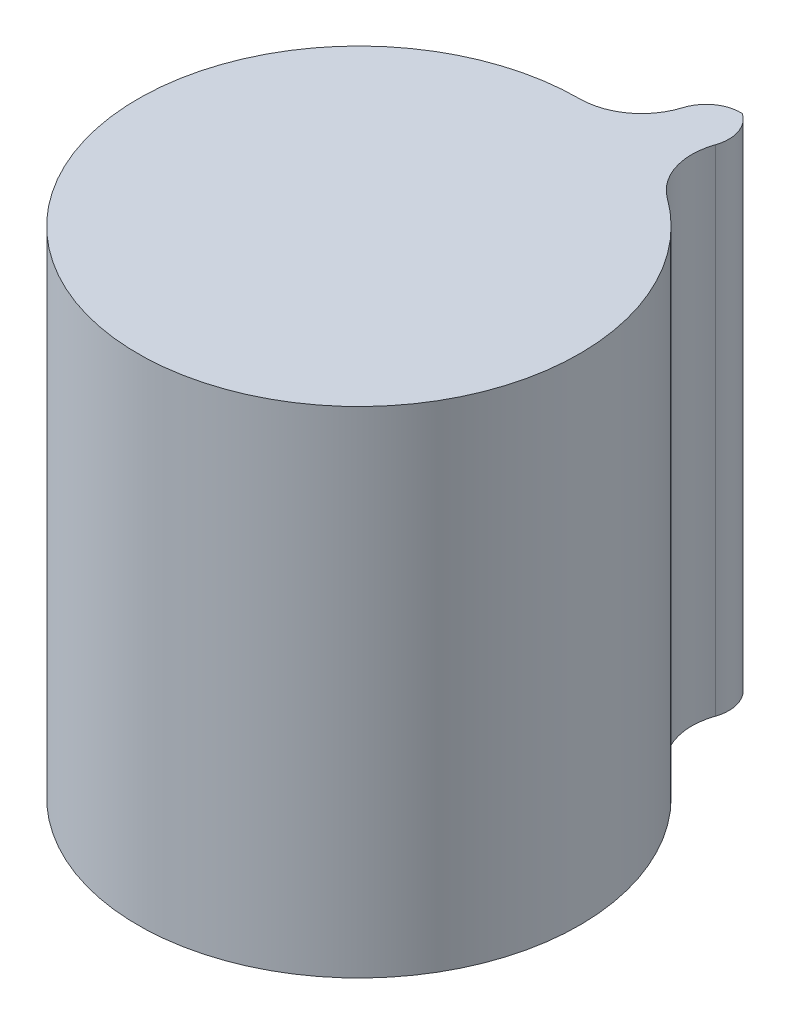
SolidWorks part; units mm, degrees
ref_plane "Front Plane" through (0, 0, 0) normal (0, 0, 1) x (1, 0, 0)
ref_plane "Top Plane" through (0, 0, 0) normal (0, 1, 0) x (1, 0, 0)
ref_plane "Right Plane" through (0, 0, 0) normal (1, 0, 0) x (0, 0, -1)
sketch "Sketch1" plane through (0, 0, 0) normal (0, 1, 0) x (1, 0, 0)
  line L0 (0, 0) -> (0, 4.3928) construction
  line L1 (0, 0) -> (2.388, 3.2869) construction
  circle A0 centre (0, 0) radius 4.3928 construction
  circle A1 centre (0, 0) radius 3.1728 construction
  circle A2 centre (0, 4.0628) radius 0.89 construction
  circle A5 centre (2.388, 3.2869) radius 0.89 construction
  arc A6 (0, 3.1728) -> (0.8515, 3.804) centre (0, 4.0628) ccw
  arc A7 (0.8515, 3.804) -> (1.5007, 4.1285) centre (1.3299, 3.6586) cw
  arc A8 (1.2125, 4.2221) -> (1.547, 3.578) centre (1.0745, 3.7416) cw
  arc A9 (1.8649, 2.5668) -> (1.547, 3.578) centre (2.388, 3.2869) cw
  arc A10 (1.5007, 4.1285) -> (1.2125, 4.2221) centre (0, 0) cw
  arc A11 (0, 3.1728) -> (1.8649, 2.5668) centre (0, 0) ccw
  dimension "D1" = 8.7856
  dimension "D3" = 1.78
  dimension "D4" = 0.5
  dimension "D2" = 1.22
  dimension "D5" = 36
extrude "Boss-Extrude1" add sketch "Sketch1" along normal mid plane 7.112 contours A6 A11 A9 A8 A7 region at (0.0335, 0, -0.1031)
ref_axis "Axis1" through (0, 3.3, 0) along (0, -1, 0)
equation "\"TEETH_NUM\" = 10"
equation "\"TOOTH_PITCH\"= 3mm"
equation "\"PITCH_LINE_OFFSET\"= .015in"
equation "\"DIAMETER_PER_GROOVE\"= \"OUTSIDE_DIAMETER\" / \"TEETH_NUM\" * 1in"
equation "\"PITCH_DIAMETER\"= ( ( \"TEETH_NUM\" * 3 - 1.31 ) / 3.1415 + .415 ) * 1mm"
equation "\"OUTSIDE_DIAMETER\"= \"PITCH_DIAMETER\" - \"PITCH_LINE_OFFSET\" * 2"
equation "\"D1@Sketch1\"=\"OUTSIDE_DIAMETER\""
equation "\"TOOTH_HEIGHT\"= 1.22mm"
equation "\"D2@Sketch1\"=\"TOOTH_HEIGHT\""
equation "\"TOOTH_DIAMETER\"= 1.78mm"
equation "\"INTERNAL_RADIUS\"= .5mm"
equation "\"D3@Sketch1\"=\"TOOTH_DIAMETER\""
equation "\"D5@Sketch1\"=360 / \"TEETH_NUM\""
equation "\"D4@Sketch1\"=\"INTERNAL_RADIUS\""
equation "\"D1@CirPattern1\"=\"TEETH_NUM\""
equation "\"BELT_GAP\"= 7mm"
equation "\"D2@Sketch2\"=\"PITCH_DIAMETER\"/2+1/32"
equation "\"D3@Sketch2\"=\"BELT_GAP\"/2"
